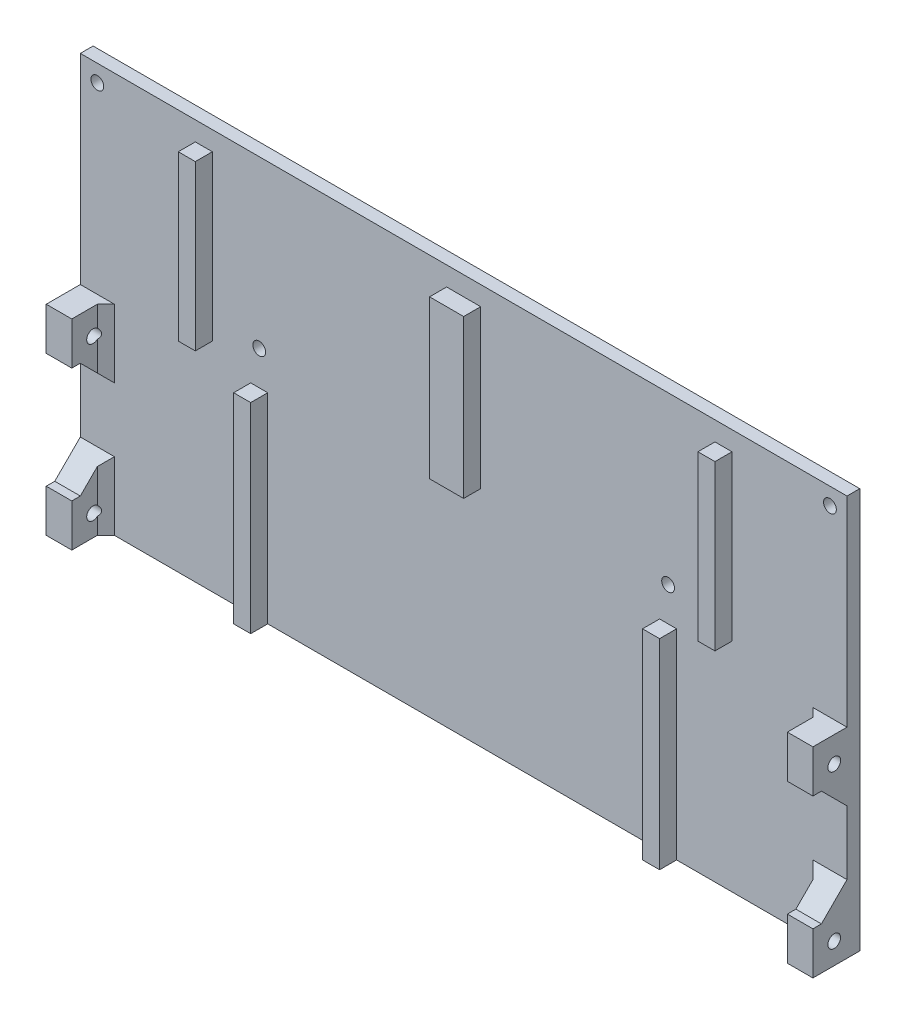
SolidWorks part; units mm, degrees
material "АБС-2020, черный"
ref_plane "Спереди" through (0, 0, 0) normal (0, 0, 1) x (1, 0, 0)
ref_plane "Сверху" through (0, 0, 0) normal (0, 1, 0) x (1, 0, 0)
ref_plane "Справа" through (0, 0, 0) normal (1, 0, 0) x (0, 0, -1)
other "Configuration Table"
sketch "Эскиз1" plane through (0, 0, 0) normal (0, 0, 1) x (1, 0, 0)
  line L1 (0, 0) -> (180, 0)
  line L2 (0, 0) -> (0, -94)
  line L3 (0, -94) -> (180, -94)
  line L4 (180, 0) -> (180, -94)
  dimension "D1" = 94
  dimension "D2" = 180
extrude "Бобышка-Вытянуть1" add sketch "Эскиз1" along normal blind 3
sketch "Эскиз2" plane through (0, 0, 3) normal (0, 0, 1) x (1, 0, 0)
  line L0 (0, 0) -> (0, -94) construction
  line L1 (0, -94) -> (6, -94)
  line L2 (0, -94) -> (0, -84)
  line L3 (0, -84) -> (6, -84)
  line L4 (6, -94) -> (6, -84)
  line L5 (180, -94) -> (174, -94)
  line L6 (180, -94) -> (180, -84)
  line L7 (180, -84) -> (174, -84)
  line L8 (174, -94) -> (174, -84)
  line L9 (0, -47) -> (6, -47)
  line L10 (0, -47) -> (0, -57)
  line L11 (0, -57) -> (6, -57)
  line L12 (6, -47) -> (6, -57)
  line L13 (180, -94) -> (180, 0) construction
  line L14 (180, -47) -> (174, -47)
  line L15 (180, -47) -> (180, -57)
  line L16 (180, -57) -> (174, -57)
  line L17 (174, -47) -> (174, -57)
  line L18 (0, -94) -> (180, -94) construction
  dimension "D1" = 10
  dimension "D2" = 6
  dimension "D3" = 10
  dimension "D4" = 6
  dimension "D5" = 47
  dimension "D6" = 6
  dimension "D7" = 6
  dimension "D8" = 47
  dimension "D9" = 10
  dimension "D10" = 10
extrude "Бобышка-Вытянуть2" add sketch "Эскиз2" along normal blind 8
chamfer "Фаска2" distance 6 angle 45 2 edges at (3, -57, 3) (177, -57, 3)
chamfer "Фаска1" distance 6 angle 45 2 edges at (3, -84, 3) (177, -84, 3)
sketch "Эскиз3" plane through (180, 0, 0) normal (1, 0, 0) x (0, 0, -1)
  line L0 (0, -94) -> (0, 0) construction
  line L1 (-11, -94) -> (0, -94) construction
  circle A0 centre (-6, -89) radius 1.5
  circle A1 centre (-6, -53) radius 1.5
  dimension "D1" = 3
  dimension "D4" = 3
  dimension "D2" = 6
  dimension "D3" = 5
  dimension "D5" = 36
extrude "Вырез-Вытянуть1" cut sketch "Эскиз3" against normal through all
sketch "Эскиз4" plane through (0, 0, 3) normal (0, 0, 1) x (1, 0, 0)
  line L0 (0, -84) -> (0, -94) construction
  line L1 (180, -94) -> (180, -84) construction
  line L2 (180, 0) -> (0, 0) construction
  circle A0 centre (4, -4) radius 1.5
  circle A1 centre (176, -4) radius 1.5
  circle A2 centre (42, -39) radius 1.5
  circle A3 centre (138, -39) radius 1.5
  dimension "D7" = 3
  dimension "D1" = 4
  dimension "D2" = 4
  dimension "D3" = 4
  dimension "D4" = 38
  dimension "D5" = 35
  dimension "D6" = 38
extrude "Вырез-Вытянуть2" cut sketch "Эскиз4" against normal through all
sketch "Эскиз5" plane through (0, 0, 3) normal (0, 0, 1) x (1, 0, 0)
  line L0 (6, -94) -> (174, -94) construction
  line L1 (40, -47) -> (44, -47)
  line L2 (40, -47) -> (40, -94)
  line L3 (40, -94) -> (44, -94)
  line L4 (44, -47) -> (44, -94)
  line L5 (180, -78) -> (180, -63) construction
  line L6 (136, -47) -> (140, -47)
  line L7 (136, -47) -> (136, -94)
  line L8 (136, -94) -> (140, -94)
  line L9 (140, -47) -> (140, -94)
  line L10 (0, -63) -> (0, -78) construction
  line L11 (180, 0) -> (0, 0) construction
  line L13 (27, -4.5) -> (27, -43)
  line L14 (27, -43) -> (31, -43)
  line L15 (31, -4.5) -> (31, -43)
  line L16 (6, -47) -> (0, -47) construction
  line L18 (149, -4.5) -> (149, -43)
  line L19 (149, -43) -> (153, -43)
  line L20 (153, -4.5) -> (153, -43)
  line L21 (27, -4.5) -> (31, -4.5)
  line L22 (149, -4.5) -> (153, -4.5)
  line L23 (0, 0) -> (0, -47) construction
  line L24 (180, -47) -> (180, 0) construction
  line L26 (86, -4.5) -> (94, -4.5)
  line L27 (86, -4.5) -> (86, -41.5)
  line L28 (86, -41.5) -> (94, -41.5)
  line L29 (94, -4.5) -> (94, -41.5)
  dimension "D12" = 8
  dimension "D1" = 4
  dimension "D2" = 4
  dimension "D3" = 40
  dimension "D4" = 40
  dimension "D5" = 4
  dimension "D6" = 4
  dimension "D7" = 27
  dimension "D8" = 4
  dimension "D9" = 4.5
  dimension "D10" = 4
  dimension "D11" = 27
  dimension "D13" = 55
  dimension "D14" = 55
extrude "Бобышка-Вытянуть3" add sketch "Эскиз5" along normal blind 4
chamfer "Фаска3" distance 2 angle 45 4 edges at (174, -86, 3) (174, -55, 3) (6, -86, 3) (6, -55, 3)
